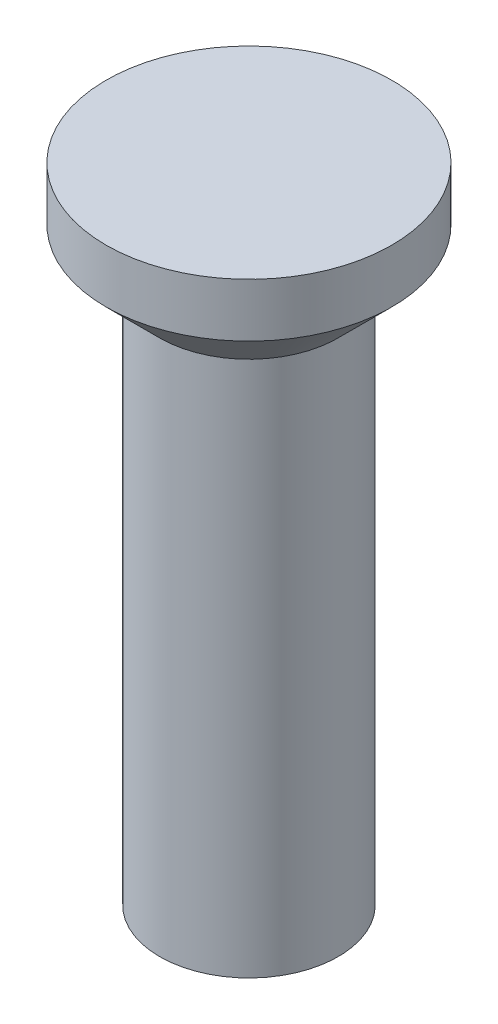
SolidWorks part; units mm, degrees
ref_plane "Спереди" through (0, 0, 0) normal (0, 0, 1) x (1, 0, 0)
ref_plane "Сверху" through (0, 0, 0) normal (0, 1, 0) x (1, 0, 0)
ref_plane "Справа" through (0, 0, 0) normal (1, 0, 0) x (0, 0, -1)
sketch "Эскиз1" plane through (0, 0, 0) normal (0, 0, 1) x (1, 0, 0)
  line L0 (0, 0) -> (25, 0)
  line L1 (25, 0) -> (25, 150)
  line L2 (25, 150) -> (40, 165)
  line L3 (40, 165) -> (40, 180)
  line L4 (40, 180) -> (0, 180)
  line L5 (0, 348.0804) -> (0, -11.7867) construction
  line L6 (0, 0) -> (0, 180)
  point P9 (0, 277.3225)
revolve "Повернуть1" add sketch "Эскиз1" angle 360 about L5
